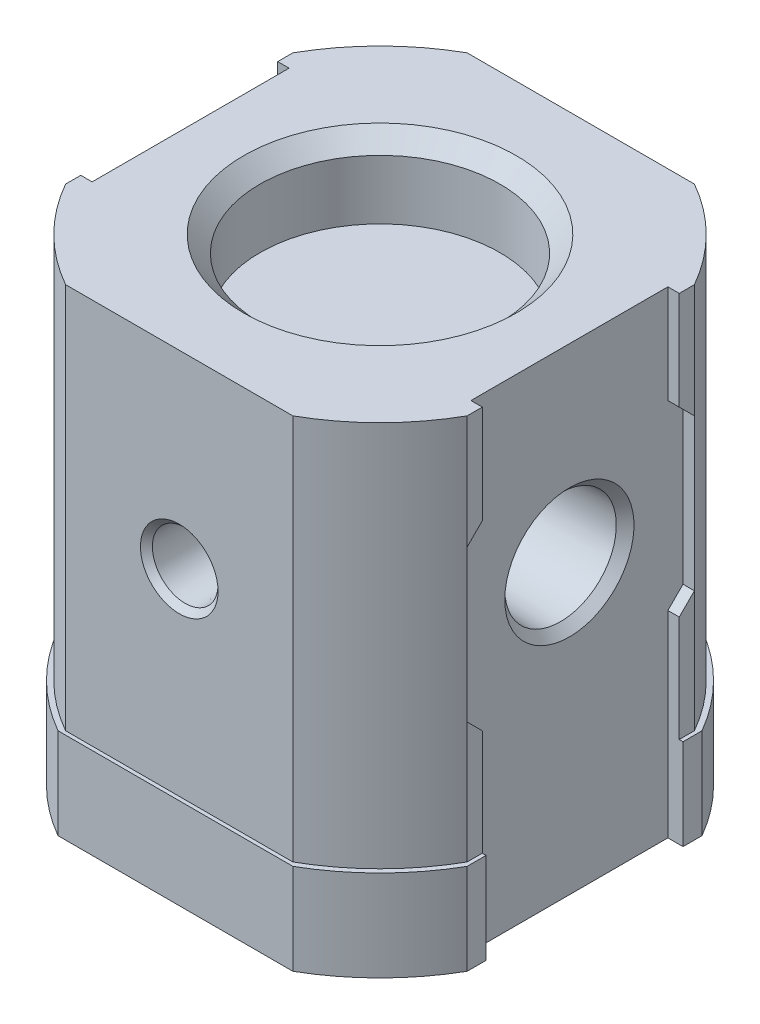
SolidWorks part; units mm, degrees
ref_plane "前视基准面" through (0, 0, 0) normal (0, 0, 1) x (1, 0, 0)
ref_plane "上视基准面" through (0, 0, 0) normal (0, 1, 0) x (1, 0, 0)
ref_plane "右视基准面" through (0, 0, 0) normal (1, 0, 0) x (0, 0, -1)
sketch "草图1" plane through (0, 0, 0) normal (0, 1, 0) x (1, 0, 0)
  line L0 (-26.5, 15) -> (-26.5, -15)
  line L1 (-15, -26.5) -> (15, -26.5)
  line L2 (26.5, -15) -> (26.5, 15)
  line L3 (15, 26.5) -> (-15, 26.5)
  arc A0 (-26.5, -15) -> (-15, -26.5) centre (0, 0) ccw
  arc A1 (15, -26.5) -> (26.5, -15) centre (0, 0) ccw
  arc A2 (26.5, 15) -> (15, 26.5) centre (0, 0) ccw
  arc A3 (-15, 26.5) -> (-26.5, 15) centre (0, 0) ccw
extrude "凸台-拉伸1" add sketch "草图1" along normal blind 63
sketch "草图2" plane through (0, 0, 0) normal (0, 1, 0) x (1, 0, 0)
  line L0 (-27, 15.5) -> (-27, -15.5)
  line L1 (-15.5, -27) -> (15.5, -27)
  line L2 (27, -15.5) -> (27, 15.5)
  line L3 (15.5, 27) -> (-15.5, 27)
  arc A0 (-27, -15.5) -> (-15.5, -27) centre (0, 0) ccw
  arc A1 (15.5, -27) -> (27, -15.5) centre (0, 0) ccw
  arc A2 (27, 15.5) -> (15.5, 27) centre (0, 0) ccw
  arc A3 (-15.5, 27) -> (-27, 15.5) centre (0, 0) ccw
extrude "凸台-拉伸2" add sketch "草图2" along normal blind 12
ref_plane "基准面4" through (-27, 0, 0) normal (1, 0, 0) x (0, 0, -1)
sketch "草图3" plane through (-27, 0, 0) normal (1, 0, 0) x (0, 0, -1)
  line L0 (-15, 48) -> (-15, 28)
  line L1 (-15, 28) -> (-13, 26)
  line L2 (-13, 26) -> (-13, 0)
  line L3 (-13, 0) -> (13, 0)
  line L4 (13, 0) -> (13, 26)
  line L5 (13, 26) -> (15, 28)
  line L6 (15, 28) -> (15, 48)
  line L7 (15, 48) -> (13, 50)
  line L8 (13, 50) -> (13, 63)
  line L9 (13, 63) -> (-13, 63)
  line L10 (-13, 63) -> (-13, 50)
  line L11 (-13, 50) -> (-15, 48)
extrude "切除-拉伸1" cut sketch "草图3" along normal blind 2
ref_plane "基准面5" through (27, 0, 0) normal (1, 0, 0) x (0, 0, -1)
sketch "草图4" plane through (27, 0, 0) normal (1, 0, 0) x (0, 0, -1)
  line L0 (-15, 48) -> (-15, 28)
  line L1 (-15, 28) -> (-13, 26)
  line L2 (-13, 26) -> (-13, 0)
  line L3 (-13, 0) -> (13, 0)
  line L4 (13, 0) -> (13, 26)
  line L5 (13, 26) -> (15, 28)
  line L6 (15, 28) -> (15, 48)
  line L7 (15, 48) -> (13, 50)
  line L8 (13, 50) -> (13, 63)
  line L9 (13, 63) -> (-13, 63)
  line L10 (-13, 63) -> (-13, 50)
  line L11 (-13, 50) -> (-15, 48)
extrude "切除-拉伸2" cut sketch "草图4" against normal blind 2
sketch "草图5" plane through (0, 0, 0) normal (0, 0, 1) x (1, 0, 0)
  line L0 (0, 63) -> (18, 63)
  line L1 (18, 63) -> (15.835, 60.835)
  line L2 (15.835, 60.835) -> (15.835, 53)
  line L3 (15.835, 53) -> (0, 53)
  line L4 (0, 53) -> (0, 63)
  line L5 (0, 53) -> (0, 63) construction
revolve "切除-旋转1" cut sketch "草图5" angle 360 about L5 reverse direction yes
cosmetic thread "装饰螺纹线1" parameters "D1"=10, "D2"=36
sketch "草图6" plane through (0, 0, 0) normal (0, 0, 1) x (1, 0, 0)
  line L0 (0, 8) -> (24.25, 8)
  line L1 (24.25, 8) -> (24.25, 4)
  line L2 (24.25, 4) -> (22, 4)
  line L3 (22, 4) -> (22, 0)
  line L4 (22, 0) -> (0, 0)
  line L5 (0, 0) -> (0, 8)
  line L6 (0, 0) -> (0, 8) construction
revolve "切除-旋转2" cut sketch "草图6" angle 360 about L6 reverse direction yes
sketch "草图7" plane through (0, 0, 0) normal (0, 0, 1) x (1, 0, 0)
  line L0 (-25, 38) -> (-25, 46.5275)
  line L1 (-25, 46.5275) -> (-23.8342, 45.3617)
  line L2 (-23.8342, 45.3617) -> (-12.574, 45.0098)
  line L3 (-12.574, 45.0098) -> (-11.7838, 45.0098)
  line L4 (-11.7838, 45.0098) -> (-7.7367, 38)
  line L5 (-7.7367, 38) -> (-25, 38)
  line L6 (-7.7367, 38) -> (-25, 38) construction
revolve "切除-旋转3" cut sketch "草图7" angle 360 about L6 reverse direction yes
sketch "草图8" plane through (0, 0, 0) normal (0, 0, 1) x (1, 0, 0)
  line L0 (7.7367, 38) -> (11.7838, 45.0098)
  line L1 (11.7838, 45.0098) -> (12.574, 45.0098)
  line L2 (12.574, 45.0098) -> (23.8342, 45.3617)
  line L3 (23.8342, 45.3617) -> (25, 46.5275)
  line L4 (25, 46.5275) -> (25, 38)
  line L5 (25, 38) -> (7.7367, 38)
  line L6 (25, 38) -> (7.7367, 38) construction
revolve "切除-旋转4" cut sketch "草图8" angle 360 about L6 reverse direction yes
sketch "草图9" plane through (0, 0, 0) normal (1, 0, 0) x (0, 0, -1)
  line L0 (-26.5, 38) -> (-26.5, 43.1211)
  line L1 (-26.5, 43.1211) -> (-25.7124, 42.3335)
  line L2 (-25.7124, 42.3335) -> (-18.3999, 42.105)
  line L3 (-18.3999, 42.105) -> (-16.8046, 42.105)
  line L4 (-16.8046, 42.105) -> (-14.4346, 38)
  line L5 (-14.4346, 38) -> (-26.5, 38)
  line L6 (-14.4346, 38) -> (-26.5, 38) construction
revolve "切除-旋转5" cut sketch "草图9" angle 360 about L6 reverse direction yes
ref_plane "基准面6" through (0, 0, 22) normal (0, 0, 1) x (1, 0, 0)
ref_plane "基准面7" through (0, 53, 0) normal (0, 1, 0) x (1, 0, 0)
ref_plane "基准面8" through (0, 63, 0) normal (0, 1, 0) x (1, 0, 0)
ref_plane "基准面9" through (0, 8, 0) normal (0, 1, 0) x (1, 0, 0)
ref_plane "gage_to_body XY" through (0, 0, 22) normal (0, 0, 1) x (1, 0, 0)
ref_plane "gage_to_body XZ" through (0, 38, 0) normal (0, -1, 0) x (-1, 0, 0)
ref_plane "gage_to_body YZ" through (0, 0, 0) normal (1, 0, 0) x (0, 0, -1)
ref_axis "gage_to_body X" through (-80.9, 38, 22) along (1, 0, 0)
ref_axis "gage_to_body Y" through (0, -50, 22) along (0, 1, 0)
ref_axis "gage_to_body Z" through (0, 38, 80.9) along (0, 0, -1)
sketch3d "gage_to_body"
  point P0 (0, 38, 22)
ref_plane "nut_to_body XY" through (0, 53, 0) normal (0, 1, 0) x (1, 0, 0)
ref_plane "nut_to_body XZ" through (0, 0, 0) normal (0, 0, 1) x (1, 0, 0)
ref_plane "nut_to_body YZ" through (0, 0, 0) normal (1, 0, 0) x (0, 0, -1)
ref_axis "nut_to_body X" through (-80.9, 53, 0) along (1, 0, 0)
ref_axis "nut_to_body Y" through (0, 53, 50) along (0, 0, -1)
ref_axis "nut_to_body Z" through (0, 50, 0) along (0, -1, 0)
sketch3d "nut_to_body"
  point P0 (0, 53, 0)
ref_plane "bracket_to_body XY" through (0, 63, 0) normal (0, 1, 0) x (1, 0, 0)
ref_plane "bracket_to_body XZ" through (0, 0, 0) normal (0, 0, 1) x (1, 0, 0)
ref_plane "bracket_to_body YZ" through (0, 0, 0) normal (1, 0, 0) x (0, 0, -1)
ref_axis "bracket_to_body X" through (-80.9, 63, 0) along (1, 0, 0)
ref_axis "bracket_to_body Y" through (0, 63, 50) along (0, 0, -1)
ref_axis "bracket_to_body Z" through (0, 50, 0) along (0, -1, 0)
sketch3d "bracket_to_body"
  point P0 (0, 63, 0)
ref_plane "case_to_body XY" through (0, 8, 0) normal (0, 1, 0) x (1, 0, 0)
ref_plane "case_to_body XZ" through (0, 0, 0) normal (0, 0, 1) x (1, 0, 0)
ref_plane "case_to_body YZ" through (0, 0, 0) normal (1, 0, 0) x (0, 0, -1)
ref_axis "case_to_body X" through (-80.9, 8, 0) along (1, 0, 0)
ref_axis "case_to_body Y" through (0, 8, 50) along (0, 0, -1)
ref_axis "case_to_body Z" through (0, 50, 0) along (0, -1, 0)
sketch3d "case_to_body"
  point P0 (0, 8, 0)
ref_plane "piston_to_body XY" through (0, 63, 0) normal (0, 1, 0) x (1, 0, 0)
ref_plane "piston_to_body XZ" through (0, 0, 0) normal (0, 0, 1) x (1, 0, 0)
ref_plane "piston_to_body YZ" through (0, 0, 0) normal (1, 0, 0) x (0, 0, -1)
ref_axis "piston_to_body X" through (-80.9, 63, 0) along (1, 0, 0)
ref_axis "piston_to_body Y" through (0, 63, 50) along (0, 0, -1)
ref_axis "piston_to_body Z" through (0, 50, 0) along (0, -1, 0)
sketch3d "piston_to_body"
  point P0 (0, 63, 0)
